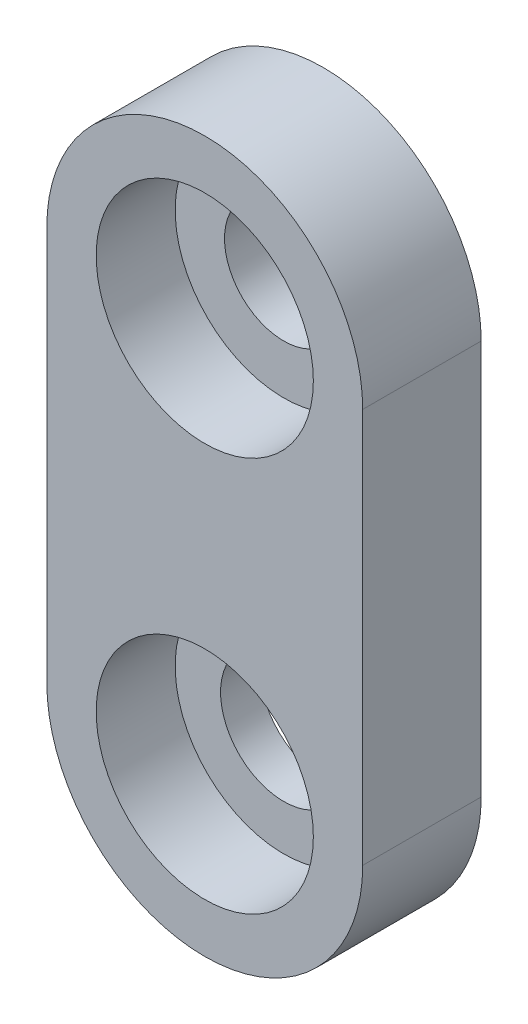
SolidWorks part; units mm, degrees
ref_plane "Front Plane" through (0, 0, 0) normal (1, 0, 0) x (0, 1, 0)
ref_plane "Top Plane" through (0, 0, 0) normal (0, 0, 1) x (0, 1, 0)
ref_plane "Right Plane" through (0, 0, 0) normal (0, 1, 0) x (-1, 0, 0)
sketch "Sketch2" plane through (0, 0, 0) normal (0, 0, 1) x (0, 1, 0)
  line L0 (0, 0) -> (12.7, 0) construction
  line L1 (0, 5.08) -> (12.7, 5.08)
  line L2 (0, -5.08) -> (12.7, -5.08)
  arc A2 (0, 5.08) -> (0, -5.08) centre (0, 0) ccw
  arc A3 (12.7, -5.08) -> (12.7, 5.08) centre (12.7, 0) ccw
  point P3 (6.35, 0)
  dimension "D1" = 10.16
  dimension "D2" = 12.7
extrude "base" add sketch "Sketch2" along normal blind 3.81
sketch "Sketch3" plane through (0, 0, 3.81) normal (0, 0, 1) x (1, 0, 0)
  circle A0 centre (0, 0) radius 2.032
  circle A1 centre (0, 12.7) radius 1.905
  dimension "D1" = 4.064
  dimension "D2" = 3.81
extrude "metric_holes" cut sketch "Sketch3" against normal up to next
sketch "Sketch4" plane through (0, 0, 3.81) normal (0, 0, 1) x (1, 0, 0)
  circle A0 centre (0, 0) radius 3.4925
  circle A1 centre (0, 12.7) radius 3.4925
  dimension "D1" = 6.985
extrude "Cut-Extrude2" cut sketch "Sketch4" against normal offset from surface (2.54 mm away) 1.27 up to face at (2.032, 0, 0)
